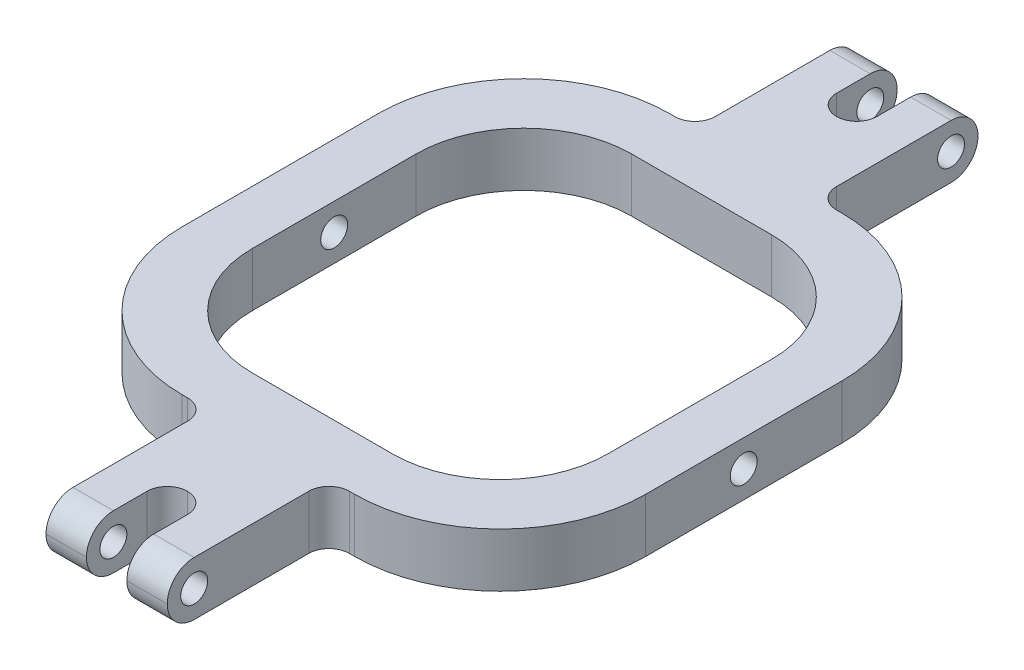
SolidWorks part; units mm, degrees
material "6063-T6"
ref_plane "Front Plane" through (0, 0, 0) normal (0, 0, 1) x (1, 0, 0)
ref_plane "Top Plane" through (0, 0, 0) normal (0, 1, 0) x (1, 0, 0)
ref_plane "Right Plane" through (0, 0, 0) normal (1, 0, 0) x (0, 0, -1)
sketch "Sketch1" plane through (0, 0, 0) normal (0, 1, 0) x (1, 0, 0)
  line L3 (20.955, -22.352) -> (-20.955, -22.352)
  line L4 (0, -22.352) -> (0, -38.2466) construction
  line L5 (-2.3813, -38.2466) -> (2.3813, -38.2466)
  line L6 (2.3813, -38.2466) -> (2.3813, -47.7716)
  line L7 (2.3813, -47.7716) -> (7.1438, -47.7716)
  line L8 (7.1438, -47.7716) -> (7.1438, -28.702)
  line L9 (7.1438, -28.702) -> (27.305, -28.702)
  line L10 (27.305, -28.702) -> (27.305, 28.702)
  line L12 (20.955, 22.352) -> (20.955, -22.352)
  line L25 (20.955, 0) -> (27.305, 0) construction
  line L26 (0, 22.352) -> (0, 38.2466) construction
  line L27 (7.1438, 28.702) -> (27.305, 28.702)
  line L28 (7.1438, 47.7716) -> (7.1438, 28.702)
  line L29 (2.3813, 47.7716) -> (7.1438, 47.7716)
  line L30 (2.3813, 38.2466) -> (2.3813, 47.7716)
  line L31 (-2.3813, 38.2466) -> (2.3813, 38.2466)
  line L32 (20.955, 22.352) -> (-20.955, 22.352)
  line L33 (-20.955, 0) -> (-27.305, 0) construction
  line L34 (-2.3813, 38.2466) -> (-2.3813, 47.7716)
  line L35 (-2.3813, 47.7716) -> (-7.1438, 47.7716)
  line L36 (-7.1438, 47.7716) -> (-7.1438, 28.702)
  line L37 (-7.1438, 28.702) -> (-27.305, 28.702)
  line L38 (-20.955, 22.352) -> (-20.955, -22.352)
  line L39 (-27.305, -28.702) -> (-27.305, 28.702)
  line L40 (-7.1438, -28.702) -> (-27.305, -28.702)
  line L41 (-7.1437, -47.7716) -> (-7.1438, -28.702)
  line L42 (-2.3812, -47.7716) -> (-7.1437, -47.7716)
  line L43 (-2.3813, -38.2466) -> (-2.3812, -47.7716)
  point P33 (0, -43.8346)
  dimension "D9" = 9.525
  dimension "D1" = 20.955
  dimension "D2" = 6.35
  dimension "D3" = 6.35
  dimension "D4" = 4.7625
  dimension "D5" = 2.3813
  dimension "D6" = 43.8346
  dimension "D7" = 22.352
  dimension "D8" = 3.937
extrude "Boss-Extrude1" add sketch "Sketch1" along normal blind 3.175 and the other way blind 3.175
sketch "Sketch2" plane through (0, 0, 0) normal (1, 0, 0) x (0, 0, -1)
  line L0 (-47.7716, -3.175) -> (-47.7716, 3.175) construction
  line L1 (47.7716, -3.175) -> (47.7716, 3.175) construction
  circle A0 centre (0, 0) radius 1.5875
  circle A1 centre (44.5966, 0) radius 1.5875
  circle A2 centre (-44.5966, 0) radius 1.5875
  dimension "D1" = 3.175
  dimension "D3" = 3.175
  dimension "D2" = 3.175
extrude "Cut-Extrude1" cut sketch "Sketch2" against normal through all both and the other way through all
fillet "Fillet1" radius 3.175 8 edges at (-4.7625, -3.175, 47.7716) (-4.7625, 3.175, 47.7716) (4.7625, 3.175, 47.7716) (4.7625, -3.175, 47.7716) (4.7625, -3.175, -47.7716) (-4.7625, -3.175, -47.7716) (4.7625, 3.175, -47.7716) (-4.7625, 3.175, -47.7716)
fillet "Fillet2" radius 12.7 4 edges at (20.955, 0, 22.352) (20.955, 0, -22.352) (-20.955, 0, -22.352) (-20.955, 0, 22.352)
fillet "Fillet4" radius 2.3813 8 edges at (7.1438, 0, 28.702) (-7.1438, 0, 28.702) (7.1438, 0, -28.702) (-7.1438, 0, -28.702) (-2.3813, 0, -38.2466) (2.3813, 0, -38.2466) (-2.3813, 0, 38.2466) (2.3813, 0, 38.2466)
fillet "Fillet3" radius 17.145 4 edges at (-27.305, 0, -28.702) (27.305, 0, -28.702) (-27.305, 0, 28.702) (27.305, 0, 28.702)
